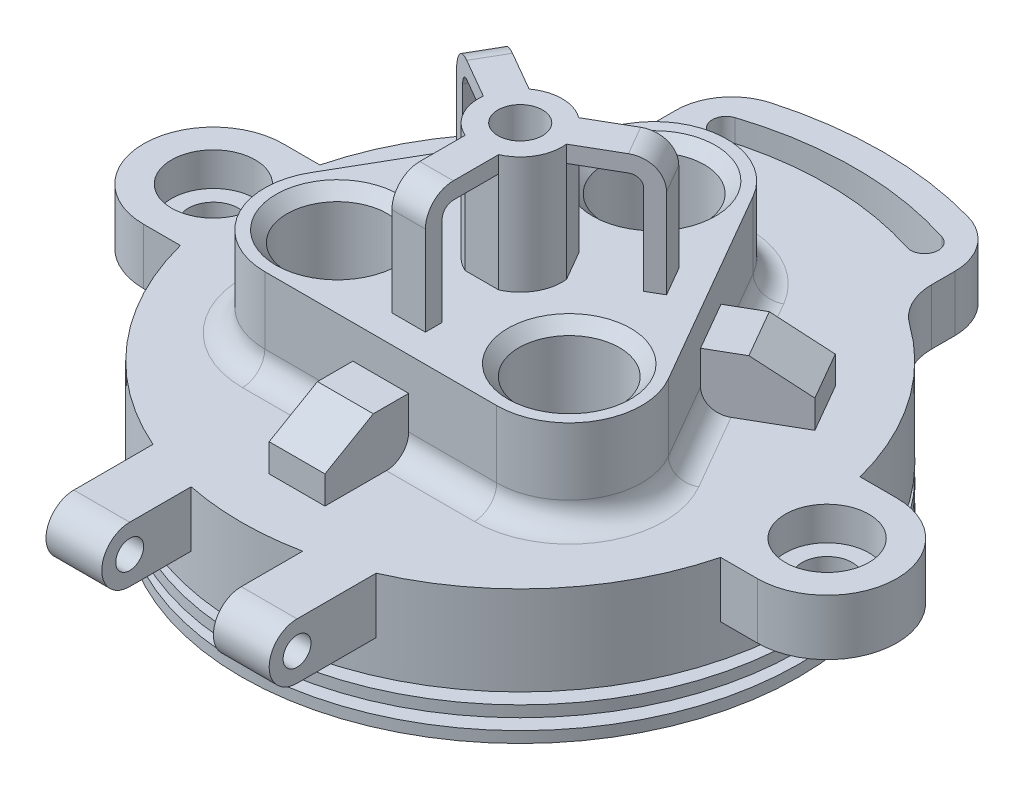
SolidWorks part; units mm, degrees
material "AISI 304"
ref_plane "Front Plane" through (0, 0, 0) normal (0, 0, 1) x (1, 0, 0)
ref_plane "Top Plane" through (0, 0, 0) normal (0, 1, 0) x (1, 0, 0)
ref_plane "Right Plane" through (0, 0, 0) normal (1, 0, 0) x (0, 0, -1)
sketch "Sketch1" plane through (0, 0, 0) normal (0, 0, 1) x (1, 0, 0)
  line L0 (0, -30.3882) -> (0, 30.3882) construction
  line L1 (0, 0) -> (50, 0)
  line L2 (50, 0) -> (50, -24)
  line L3 (50, -24) -> (45, -24)
  line L4 (45, -24) -> (45, -9)
  line L5 (45, -9) -> (0, -9)
  line L6 (0, -9) -> (0, 0)
  line L7 (45, -24) -> (3.1979, -24) construction
  dimension "D1" = 24
  dimension "D2" = 100
  dimension "D3" = 5
  dimension "D4" = 15
revolve "Revolve1" add sketch "Sketch1" angle 360 about L0
sketch "Sketch2" plane through (0, 0, 0) normal (0, 1, 0) x (1, 0, 0)
  line L0 (-48.4123, 12.5) -> (-55, 12.5)
  line L1 (-55, -12.5) -> (-48.4123, -12.5)
  line L2 (-48.4123, -12.5) -> (-48.4123, 12.5)
  line L3 (0, 0) -> (-114.3844, 0) construction
  line L4 (0, 0) -> (0, 52.6625) construction
  line L5 (48.4123, -12.5) -> (48.4123, 12.5)
  line L6 (55, -12.5) -> (48.4123, -12.5)
  line L7 (48.4123, 12.5) -> (55, 12.5)
  circle A0 centre (0, 0) radius 50 construction
  arc A1 (-55, 12.5) -> (-55, -12.5) centre (-55, 0) ccw
  arc A3 (55, 12.5) -> (55, -12.5) centre (55, 0) cw
  dimension "D1" = 25
  dimension "D2" = 110
extrude "Boss-Extrude1" add sketch "Sketch2" against normal blind 10
sketch "Sketch3" plane through (0, 0, 0) normal (0, 1, 0) x (1, 0, 0)
  line L0 (0, 50) -> (0, -25) construction
  line L1 (32.0429, -5.5) -> (11.2583, 30.5)
  line L2 (-11.2583, 30.5) -> (-32.0429, -5.5)
  line L3 (-20.7846, -25) -> (20.7846, -25)
  line L4 (-43.3013, -25) -> (21.6506, 12.5) construction
  line L5 (43.3013, -25) -> (-21.6506, 12.5) construction
  line L6 (-20.7846, -25) -> (-43.3013, -25) construction
  line L7 (-43.3013, -25) -> (-32.0429, -5.5) construction
  line L8 (20.7846, -25) -> (43.3013, -25) construction
  line L9 (43.3013, -25) -> (32.0429, -5.5) construction
  line L10 (11.2583, 30.5) -> (0, 50) construction
  line L11 (0, 50) -> (-11.2583, 30.5) construction
  circle A0 centre (0, 0) radius 25 construction
  arc A1 (48.4123, 12.5) -> (-48.4123, 12.5) centre (0, 0) ccw construction
  circle A5 centre (0, 24) radius 9
  arc A6 (11.2583, 30.5) -> (-11.2583, 30.5) centre (0, 24) ccw
  circle A7 centre (20.7846, -12) radius 9
  arc A8 (20.7846, -25) -> (32.0429, -5.5) centre (20.7846, -12) ccw
  circle A9 centre (-20.7846, -12) radius 9
  arc A10 (-32.0429, -5.5) -> (-20.7846, -25) centre (-20.7846, -12) ccw
  arc A11 (-48.4123, -12.5) -> (48.4123, -12.5) centre (0, 0) ccw construction
  point P26 (0, 0)
  dimension "D1" = 24
  dimension "D2" = 4
  dimension "D3" = 3
extrude "Boss-Extrude2" add sketch "Sketch3" along normal blind 16
fillet "Fillet1" radius 4 6 edges at (-32.0429, 0, 18.5) (-21.6506, 0, -12.5) (0, 0, -37) (21.6506, 0, -12.5) (32.0429, 0, 18.5) (0, 0, 25)
chamfer "Chamfer1" distance 2 angle 45 3 edges at (0, 16, -15) (-20.7846, 16, 21) (20.7846, 16, 21)
sketch "Sketch5" plane through (0, -9, 0) normal (0, -1, 0) x (1, 0, 0)
  line L0 (-43.3013, 25) -> (-20.7846, 25) construction
  line L1 (-43.3013, 25) -> (-32.0429, 5.5) construction
  circle A1 centre (-20.7846, 12) radius 13
  arc A3 (-20.7846, 25) -> (-32.0429, 5.5) centre (-20.7846, 12) ccw construction
  circle A5 centre (0, 0) radius 50 construction
  circle A6 centre (-20.7846, 12) radius 9 construction
  dimension "D2" = 4
  dimension "D1" = 60
extrude "Boss-Extrude3" add sketch "Sketch5" along normal blind 10
sketch "Sketch4" plane through (0, 16, 0) normal (0, 1, 0) x (1, 0, 0)
  circle A1 centre (0, 24) radius 9 construction
  circle A2 centre (0, 24) radius 9
  circle A3 centre (20.7846, -12) radius 9 construction
  circle A4 centre (-20.7846, -12) radius 9 construction
  circle A5 centre (20.7846, -12) radius 9
  circle A6 centre (-20.7846, -12) radius 9
extrude "Cut-Extrude1" cut sketch "Sketch4" against normal through all both and the other way through all
sketch "Sketch6" plane through (0, 0, 0) normal (0, 0, 1) x (1, 0, 0)
  line L0 (0, 0) -> (0, 45.7801) construction
pattern_circular "CirPattern1" count 3 over 360 about axis through (0, 0, 0) along (0, 1, 0) of "Boss-Extrude3"
sketch "Sketch7" plane through (0, 16, 0) normal (0, 1, 0) x (1, 0, 0)
  circle A0 centre (0, 24) radius 9 construction
  circle A1 centre (20.7846, -12) radius 9 construction
  circle A2 centre (0, 24) radius 9
  circle A3 centre (20.7846, -12) radius 9
extrude "Cut-Extrude2" cut sketch "Sketch7" against normal through all both and the other way through all
hole_wizard "CBORE for M8 Hex Head Machine Screw1" positions "Sketch8" profile "Sketch9" counterbore size "M8" standard "ANSI Metric" end condition through all
sketch "Sketch8" plane through (0, 0, 0) normal (0, 1, 0) x (1, 0, 0)
  arc A0 (55, -12.5) -> (55, 12.5) centre (55, 0) ccw construction
  arc A1 (-55, 12.5) -> (-55, -12.5) centre (-55, 0) ccw construction
  point P0 (-55, 0)
  point P2 (55, 0)
sketch "Sketch9" plane through (-55, 0, 0) normal (1, 0, 0) x (0, 0, 1)
  line L0 (0, 0) -> (0, 24)
  line L1 (0, 24) -> (4.5, 24)
  line L3 (4.5, 24) -> (4.5, 6)
  line L4 (4.5, 6) -> (7.5, 6)
  line L5 (7.5, 6) -> (7.5, 0)
  line L7 (7.5, 0) -> (0, 0)
  line L11 (0, -6.35) -> (0, 107.95) construction
  dimension "Thru Hole Dia." = 9
  dimension "Thru Hole Depth" = 24
  dimension "C'Bore Dia." = 15
  dimension "C'Bore Depth" = 6
sketch "Sketch10" plane through (0, 16, 0) normal (0, 1, 0) x (1, 0, 0)
  line L0 (-16.9907, 4.5712) -> (-12.4542, 12.4288)
  line L2 (-11.2583, 30.5) -> (-32.0429, -5.5) construction
  line L3 (-11.2583, 30.5) -> (-32.0429, -5.5) construction
  line L4 (12.4542, 12.4288) -> (16.9907, 4.5712)
  line L5 (4.5365, -17) -> (-4.5365, -17)
  line L6 (32.0429, -5.5) -> (11.2583, 30.5) construction
  line L7 (-20.7846, -25) -> (20.7846, -25) construction
  arc A0 (-12.4542, 12.4288) -> (12.4542, 12.4288) centre (0, 24) ccw
  circle A1 centre (0, 24) radius 9 construction
  arc A2 (16.9907, 4.5712) -> (4.5365, -17) centre (20.7846, -12) ccw
  arc A3 (-4.5365, -17) -> (-16.9907, 4.5712) centre (-20.7846, -12) ccw
  point P20 (0, 0)
  dimension "D2" = 8
  dimension "D1" = 8
  dimension "D4" = 8
  dimension "D5" = 8
  dimension "D3" = 3
extrude "Cut-Extrude3" [suppressed] cut sketch "Sketch10" against normal up to surface (16 mm away)
sketch "Sketch11" plane through (0, 0, 0) normal (0, 0, 1) x (1, 0, 0)
  line L0 (-50, -10) -> (-50, -24) construction
  line L1 (-50, -16) -> (-47, -16)
  line L2 (-50, -16) -> (-50, -18)
  line L3 (-50, -18) -> (-47, -18)
  line L4 (-47, -16) -> (-47, -18)
  line L5 (-50, -24) -> (50, -24) construction
  line L6 (-50, -20) -> (-47, -20)
  line L7 (-50, -20) -> (-50, -22)
  line L8 (-50, -22) -> (-47, -22)
  line L9 (-47, -20) -> (-47, -22)
  line L10 (0, 0) -> (0, -36.9302) construction
  dimension "D1" = 2
  dimension "D2" = 2
  dimension "D3" = 2
  dimension "D4" = 2
  dimension "D5" = 47
revolve "Cut-Revolve1" cut sketch "Sketch11" angle 360 about L10
sketch "Sketch12" plane through (0, 0, 0) normal (1, 0, 0) x (0, 0, -1)
  line L0 (-25, 10) -> (-31.3397, 10)
  line L1 (-25, 16) -> (-25, 4) construction
  line L2 (-31.3397, 10) -> (-40, 5)
  line L3 (-40, 5) -> (-40, 0)
  line L4 (-12.5, 0) -> (-50, 0) construction
  line L5 (-40, 0) -> (-25, 0)
  line L6 (-3.5, 0) -> (-29, 0) construction
  line L7 (-25, 0) -> (-25, 10)
  dimension "D1" = 40
  dimension "D2" = 210
  dimension "D3" = 5
  dimension "D4" = 10
extrude "Boss-Extrude4" add sketch "Sketch12" along normal mid plane 10
pattern_circular "CirPattern2" count 3 over 360 about axis through (0, 0, 0) along (0, 1, 0) of "Boss-Extrude4" reverse direction yes
ref_plane "Plane1" through (10, 0, 0) normal (1, 0, 0) x (0, 0, -1)
sketch "Sketch14" plane through (10, 0, 0) normal (1, 0, 0) x (0, 0, -1)
  line L0 (-60, 0) -> (-45, 0)
  line L1 (-45, 0) -> (-45, -10)
  line L2 (-45, -10) -> (-60, -10)
  line L4 (-12.5, 0) -> (-50, 0) construction
  arc A0 (-60, -10) -> (-60, 0) centre (-60, -5) cw
  circle A1 centre (-60, -5) radius 2.5
  point P6 (-65, -5)
  dimension "D2" = 5
  dimension "D1" = 10
  dimension "D3" = 65
  dimension "D4" = 15
extrude "Boss-Extrude5" add sketch "Sketch14" along normal blind 10
mirror "Mirror1" about plane through (0, 0, 0) normal (1, 0, 0) of "Boss-Extrude5"
sketch "Sketch15" plane through (0, 0, 0) normal (0, 1, 0) x (1, 0, 0)
  line L0 (-25, 43.3013) -> (-25, 60)
  line L1 (25, 60) -> (25, 43.3013)
  line L2 (0, 0) -> (0, 94.5824) construction
  line L3 (0, 0) -> (27.6828, 85.199) construction
  line L4 (0, 0) -> (-29.0762, 89.4873) construction
  arc A0 (48.4123, 12.5) -> (-48.4123, 12.5) centre (0, 0) ccw construction
  arc A1 (-25, 60) -> (25, 60) centre (0, 0) cw
  arc A2 (25, 43.3013) -> (-25, 43.3013) centre (0, 0) ccw
  arc A3 (-17.7685, 54.6857) -> (17.7685, 54.6857) centre (0, 0) cw construction
  arc A4 (18.541, 57.0634) -> (-18.541, 57.0634) centre (0, 0) ccw
  arc A5 (16.9959, 52.3081) -> (-16.9959, 52.3081) centre (0, 0) ccw
  arc A6 (16.9959, 52.3081) -> (18.541, 57.0634) centre (17.7685, 54.6857) ccw
  arc A7 (-18.541, 57.0634) -> (-16.9959, 52.3081) centre (-17.7685, 54.6857) ccw
  point P10 (0, 65)
  point P14 (0, 57.5)
  dimension "D1" = 65
  dimension "D4" = 60
  dimension "D5" = 55
  dimension "D2" = 50
  dimension "D3" = 18
extrude "Boss-Extrude6" add sketch "Sketch15" against normal blind 10
sketch "Sketch16" plane through (0, 16, 0) normal (0, 1, 0) x (1, 0, 0)
  circle A0 centre (0, 0) radius 7.5
  dimension "D1" = 15
extrude "Boss-Extrude7" add sketch "Sketch16" along normal blind 21
sketch "Sketch17" plane through (0, 37, 0) normal (0, 1, 0) x (1, 0, 0)
  circle A0 centre (0, 0) radius 4
  dimension "D1" = 8
extrude "Cut-Extrude4" cut sketch "Sketch17" against normal through all both and the other way through all
sketch "Sketch19" plane through (0, 0, 0) normal (1, 0, 0) x (0, 0, -1)
  line L0 (-5.5, 37) -> (-15, 37)
  line L1 (-20, 32) -> (-20, 15.6311)
  line L2 (-20, 15.6311) -> (-17, 15.6311)
  line L3 (-17, 15.6311) -> (-17, 32)
  line L4 (-15, 34) -> (-5.5, 34)
  line L5 (-5.5, 34) -> (-5.5, 37)
  line L6 (7.5, 37) -> (-7.5, 37) construction
  line L7 (0, 0) -> (0, 45.7801) construction
  arc A0 (-15, 37) -> (-20, 32) centre (-15, 32) ccw
  arc A1 (-17, 32) -> (-15, 34) centre (-15, 32) cw
  point P10 (-16.4142, 33.4142)
  point P11 (-18.5355, 35.5355)
  dimension "D3" = 5
  dimension "D1" = 3
  dimension "D2" = 3
  dimension "D4" = 9.5
  dimension "D5" = 3
  dimension "D6" = 20
extrude "Boss-Extrude9" add sketch "Sketch19" along normal mid plane 6
sketch "Sketch21" plane through (0, 0, 0) normal (1, 0, 0) x (0, 0, -1)
  line L0 (-17, 16) -> (-17, 32) construction
  line L2 (-17, 16) -> (-17, 32)
  line L4 (-17, 16) -> (-6.8739, 16)
  line L5 (-5.5, 16) -> (-25, 16) construction
  line L6 (-6.8739, 16) -> (-6.8739, 34)
  line L7 (-6.8739, 34) -> (-15, 34)
  line L11 (-6.8739, 37) -> (-6.8739, 34) construction
  arc A0 (-15, 34) -> (-17, 32) centre (-15, 32) ccw construction
  arc A1 (-15, 34) -> (-17, 32) centre (-15, 32) ccw
extrude "Cut-Extrude5" cut sketch "Sketch21" against normal mid plane 6
pattern_circular "CirPattern3" count 3 over 360 about axis through (0, 0, 0) along (0, 1, 0) of "Boss-Extrude9", "Cut-Extrude5" reverse direction yes
fillet "Fillet6" radius 10 1 edges at (25, -5, -43.3013) type face fillet first side face at (0, -5, 10.1367) second side face at (25, -5, -51.6506)
fillet "Fillet7" radius 10 1 edges at (25, -5, -60) type face fillet first side face at (0, -5, -62.5) second side face at (25, -5, -54.367)
fillet "Fillet8" radius 10 1 edges at (-25, -5, -60) type face fillet first side face at (-25, -5, -51.6506) second side face at (-3.7437, -5, -63.0769)
fillet "Fillet9" radius 10 1 edges at (-25, -5, -43.3013) type face fillet first side face at (-25, -5, -48.1081) second side face at (0.4049, -5, 10.3748)
equation "\"A\"= 100"
equation "\"B\"= 40"
equation "\"C\"= 110"
equation "\"D\"= 24"
equation "\"X\"= \"A\" / 4"
equation "\"D1@Sketch1\"=\"D\""
equation "\"D2@Sketch1\"=\"A\""
equation "\"D1@Sketch2\"=\"X\""
equation "\"D2@Sketch2\"=\"C\""
equation "\"Y\"= \"D\" * 1.5 - 15"
equation "\"D1@Boss-Extrude7\"=\"Y\""
